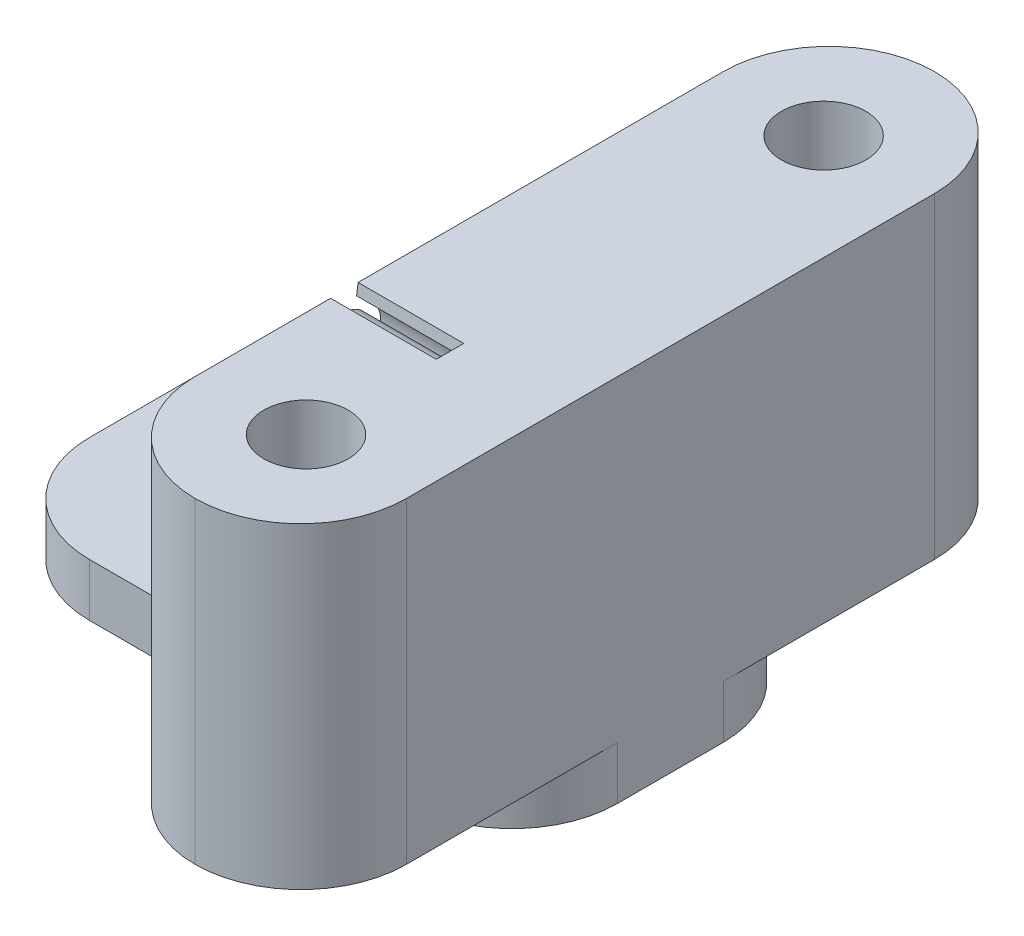
SolidWorks part; units mm, degrees
ref_plane "Front Plane" through (0, 0, 0) normal (0, 0, 1) x (1, 0, 0)
ref_plane "Top Plane" through (0, 0, 0) normal (0, 1, 0) x (1, 0, 0)
ref_plane "Right Plane" through (0, 0, 0) normal (1, 0, 0) x (0, 0, -1)
sketch "Sketch2" plane through (0, 0, 0) normal (0, 1, 0) x (1, 0, 0)
  line L1 (-3.5224, 29.7612) -> (16.4776, 29.7612)
  line L2 (-3.5224, 29.7612) -> (-3.5224, -40.2388)
  line L3 (-3.5224, -40.2388) -> (16.4776, -40.2388)
  line L4 (16.4776, 29.7612) -> (16.4776, -40.2388)
  dimension "D1" = 70
  dimension "D2" = 20
extrude "Boss-Extrude1" add sketch "Sketch2" along normal blind 30
sketch "Sketch3" plane through (0, 30, 0) normal (0, 1, 0) x (1, 0, 0)
  line L1 (-3.5224, -40.2388) -> (16.4776, -40.2388) construction
  line L3 (16.4776, -40.2388) -> (16.4776, 29.7612) construction
  line L4 (16.4776, 29.7612) -> (-3.5224, 29.7612) construction
  circle A0 centre (6.4776, 19.2612) radius 4
  circle A1 centre (6.4776, -29.7388) radius 4
  dimension "D13" = 8
  dimension "D14" = 8
  dimension "D2" = 49
  dimension "D3" = 10.5
  dimension "D4" = 10.5
  dimension "D5" = 10
extrude "Cut-Extrude1" cut sketch "Sketch3" against normal blind 20
sketch "Sketch4" plane through (-3.5224, 0, 0) normal (-1, 0, 0) x (0, 0, 1)
  line L0 (8.1636, 30.0512) -> (8.1636, 15.6029) construction
  line L1 (-23.743, 30.1264) -> (40.1453, 30.1264)
  line L2 (-23.743, 30.1264) -> (-23.743, 15.6782)
  line L3 (-23.743, 15.6782) -> (40.1453, 15.6782)
  line L4 (40.1453, 30.1264) -> (40.1453, 15.6782)
  line L5 (14.95, 28.9694) -> (14.7857, 30.2017)
  line L6 (14.7857, 30.2017) -> (17.4195, 30.2017)
  line L7 (17.4195, 30.2017) -> (17.3442, 28.9224)
  circle A0 centre (16.1636, 25.6866) radius 2.5
  circle A1 centre (16.1636, 25.6866) radius 3.5
  dimension "D2" = 5
  dimension "D3" = 7
  dimension "D1" = 8
extrude "Cut-Extrude2" cut sketch "Sketch4" against normal blind 10
fillet "Fillet1" radius 10 4 edges at (-3.5224, 15, -29.7612) (16.4776, 15, -29.7612) (16.4776, 15, 40.2388) (-3.5224, 15, 40.2388)
sketch "Sketch6" plane through (0, 0, 0) normal (0, -1, 0) x (1, 0, 0)
  line L0 (16.4776, 30.2388) -> (16.4776, -19.7612) construction
  line L1 (-33.5224, 20.2388) -> (16.4776, 20.2388)
  line L2 (-33.5224, 20.2388) -> (-33.5224, -9.7612)
  line L3 (-33.5224, -9.7612) -> (16.4776, -9.7612)
  line L4 (16.4776, 20.2388) -> (16.4776, -9.7612)
  arc A0 (6.4776, 40.2388) -> (-3.5224, 30.2388) centre (6.4776, 30.2388) ccw construction
  dimension "D1" = 30
  dimension "D2" = 10
  dimension "D3" = 50
  dimension "D4" = 0
extrude "Boss-Extrude3" add sketch "Sketch6" along normal blind 5
sketch "Sketch7" plane through (0, -5, 0) normal (0, -1, 0) x (1, 0, 0)
  line L0 (16.4776, 20.2388) -> (-33.5224, 20.2388) construction
  line L1 (-3.5224, 20.2388) -> (-3.5224, 30.2388) construction
  circle A0 centre (-13.5224, 5.2388) radius 2.5
  dimension "D1" = 5
  dimension "D2" = 15
  dimension "D3" = 10
extrude "Cut-Extrude3" cut sketch "Sketch7" against normal blind 10
fillet "Fillet3" radius 10 4 edges at (-33.5224, -2.5, -9.7612) (-33.5224, -2.5, 20.2388) (16.4776, -2.5, -9.7612) (16.4776, -2.5, 20.2388)
